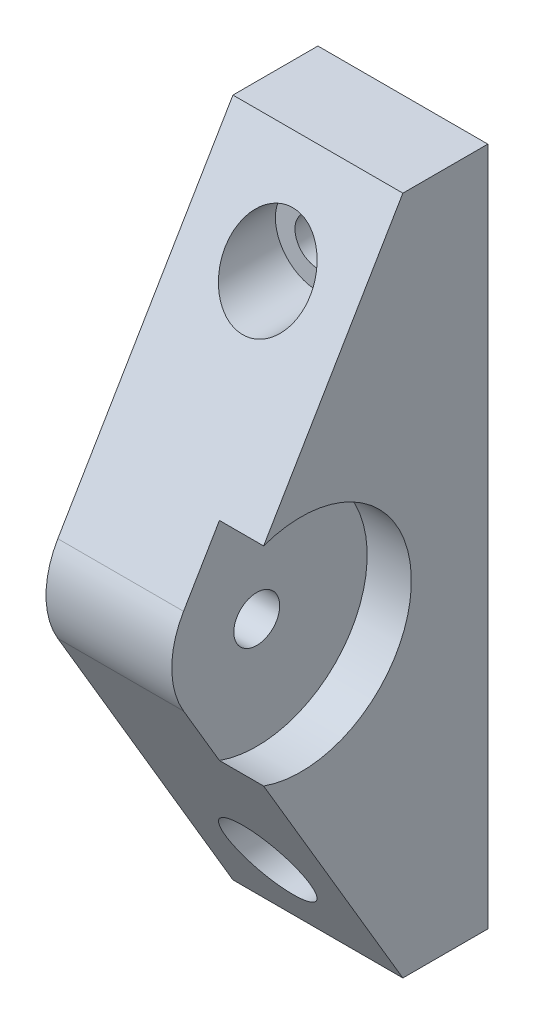
SolidWorks part; units mm, degrees
material "ABS"
ref_plane "xy" through (0, 0, 0) normal (0, 0, 1) x (1, 0, 0)
ref_plane "xz" through (0, 0, 0) normal (0, 1, 0) x (1, 0, 0)
ref_plane "yz" through (0, 0, 0) normal (1, 0, 0) x (0, 0, -1)
ref_axis "x" through (-11, 0, 0) along (1, 0, 0)
ref_axis "y" through (0, 14, 0) along (0, -1, 0)
ref_axis "z" through (0, 0, -1.65) along (0, 0, 1)
sketch "Sketch1" plane through (0, 0, 0) normal (0, 0, 1) x (1, 0, 0)
  line L0 (0, -18.15) -> (0, 18.15) construction
  line L1 (-10, 10) -> (10, 10)
  line L2 (-10, 10) -> (-10, -70)
  line L3 (-10, -70) -> (10, -70)
  line L4 (10, 10) -> (10, -70)
  circle A0 centre (0, 0) radius 2.7
  circle A1 centre (0, -60) radius 2.7
  point P7 (0, 10)
  dimension "D1" = 5.4
  dimension "D2" = 10
  dimension "D3" = 20
  dimension "D4" = 80
  dimension "D5" = 10
extrude "Boss-Extrude1" add sketch "Sketch1" along normal blind 10
sketch "Sketch2" plane through (0, 0, 0) normal (1, 0, 0) x (0, 0, -1)
  line L0 (-10, 10) -> (-30.6115, -24.9165)
  line L1 (-30.6115, -35.0835) -> (-10, -70)
  line L2 (-10, -70) -> (-10, 10)
  line L3 (0, 11) -> (0, -11) construction
  arc A0 (-30.6115, -24.9165) -> (-30.6115, -35.0835) centre (-22, -30) ccw
  circle A1 centre (-22, -30) radius 2.7
  dimension "D1" = 5.4
  dimension "D2" = 10
  dimension "D3" = 30
  dimension "D4" = 22
extrude "Boss-Extrude2" add sketch "Sketch2" along normal mid plane 20
sketch "Sketch3" plane through (0, 0, 10) normal (0, 0, -1) x (-1, 0, 0)
  circle A0 centre (0, -60) radius 5
  circle A1 centre (0, 0) radius 5
  dimension "D1" = 10
extrude "Cut-Extrude1" cut sketch "Sketch3" against normal through all
sketch "Sketch4" plane through (10, 0, 0) normal (1, 0, 0) x (0, 0, -1)
  circle A0 centre (-22, -30) radius 13
  dimension "D1" = 26
extrude "Cut-Extrude2" cut sketch "Sketch4" against normal blind 5.2
